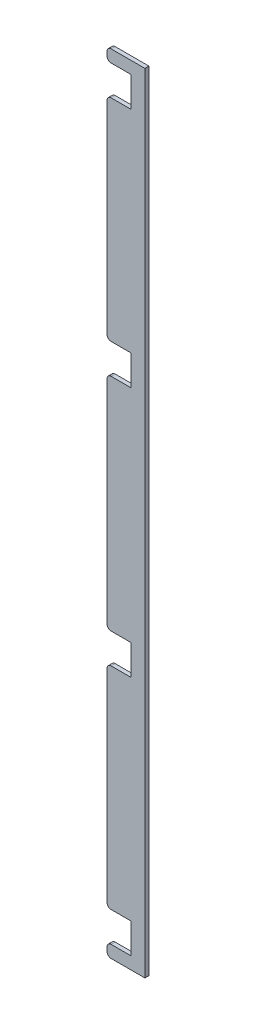
SolidWorks part; units mm, degrees
ref_plane "Front Plane" through (0, 0, 0) normal (0, 0, 1) x (1, 0, 0)
ref_plane "Top Plane" through (0, 0, 0) normal (0, 1, 0) x (1, 0, 0)
ref_plane "Right Plane" through (0, 0, 0) normal (1, 0, 0) x (0, 0, -1)
sketch "Sketch1" plane through (0, 0, 0) normal (0, 0, 1) x (1, 0, 0)
  line L0 (0, -182.5952) -> (-4.5, -182.5952)
  line L2 (0, 13.4048) -> (0, -182.5952)
  line L6 (-4.5, 10.3548) -> (-3.5, 10.3548)
  line L7 (-3.5, 10.3548) -> (-3.5, 2.8548)
  line L8 (0, 2.4048) -> (0, -5.5952) construction
  line L9 (-3.5, 2.8548) -> (-4.5, 2.8548)
  line L10 (-4.5, -49.6452) -> (-3.5, -49.6452)
  line L11 (-3.5, -49.6452) -> (-3.5, -57.1452)
  line L12 (-3.5, -57.1452) -> (-4.5, -57.1452)
  line L13 (-4.5, -112.0452) -> (-3.5, -112.0452)
  line L14 (-3.5, -112.0452) -> (-3.5, -119.5452)
  line L15 (-3.5, -119.5452) -> (-4.5, -119.5452)
  line L16 (-4.5, -172.0452) -> (-3.5, -172.0452)
  line L17 (-3.5, -172.0452) -> (-3.5, -179.5452)
  line L18 (-3.5, -179.5452) -> (-4.5, -179.5452)
  line L100 (-8.4, 10.3548) -> (-4.5, 10.3548)
  line L101 (-4.5, 10.3548) -> (-4.5, 2.8548)
  line L102 (-4.5, 2.8548) -> (-8.4, 2.8548)
  line L103 (-9.4, 1.8548) -> (-9.4, -48.6452)
  line L104 (-8.4, -49.6452) -> (-4.5, -49.6452)
  line L105 (-4.5, -49.6452) -> (-4.5, -57.1452)
  line L106 (-4.5, -57.1452) -> (-8.4, -57.1452)
  line L107 (-9.4, -58.1452) -> (-9.4, -111.0452)
  line L108 (-8.4, -112.0452) -> (-4.5, -112.0452)
  line L109 (-4.5, -112.0452) -> (-4.5, -119.5452)
  line L110 (-4.5, -119.5452) -> (-8.4, -119.5452)
  line L111 (-9.4, -120.5452) -> (-9.4, -171.0452)
  line L112 (-8.4, -172.0452) -> (-4.5, -172.0452)
  line L113 (-4.5, -172.0452) -> (-4.5, -179.5452)
  line L114 (-4.5, -179.5452) -> (-8.4, -179.5452)
  line L115 (-9.4, -180.5452) -> (-9.4, -181.5952)
  line L116 (-8.4, -182.5952) -> (-4.5, -182.5952)
  line L117 (-4.5, -182.5952) -> (-4.5, -191.5952)
  line L118 (-4.5, -191.5952) -> (78.5, -191.5952)
  line L119 (78.5, -191.5952) -> (78.5, -182.5952)
  line L120 (78.5, -182.5952) -> (82.4, -182.5952)
  line L121 (83.4, -181.5952) -> (83.4, -180.5452)
  line L122 (82.4, -179.5452) -> (78.5, -179.5452)
  line L123 (78.5, -179.5452) -> (78.5, -172.0452)
  line L124 (78.5, -172.0452) -> (82.4, -172.0452)
  line L125 (83.4, -171.0452) -> (83.4, -120.5452)
  line L126 (82.4, -119.5452) -> (78.5, -119.5452)
  line L127 (78.5, -119.5452) -> (78.5, -112.0452)
  line L128 (78.5, -112.0452) -> (82.4, -112.0452)
  line L129 (83.4, -111.0452) -> (83.4, -58.1452)
  line L130 (82.4, -57.1452) -> (78.5, -57.1452)
  line L131 (78.5, -57.1452) -> (78.5, -49.6452)
  line L132 (78.5, -49.6452) -> (82.4, -49.6452)
  line L133 (83.4, -48.6452) -> (83.4, 1.8548)
  line L134 (82.4, 2.8548) -> (78.5, 2.8548)
  line L135 (78.5, 2.8548) -> (78.5, 10.3548)
  line L136 (78.5, 10.3548) -> (82.4, 10.3548)
  line L137 (83.4, 11.3548) -> (83.4, 12.4048)
  line L138 (82.4, 13.4048) -> (78.5, 13.4048)
  line L139 (78.5, 13.4048) -> (78.5, 22.4048)
  line L140 (78.5, 22.4048) -> (-4.5, 22.4048)
  line L141 (-4.5, 22.4048) -> (-4.5, 13.4048)
  line L142 (-4.5, 13.4048) -> (-8.4, 13.4048)
  line L143 (-9.4, 12.4048) -> (-9.4, 11.3548)
  line L144 (-8.4, 10.3548) -> (-4.5, 10.3548)
  line L145 (-4.5, 10.3548) -> (-4.5, 2.8548)
  line L146 (-4.5, 2.8548) -> (-8.4, 2.8548)
  line L147 (-9.4, 1.8548) -> (-9.4, -48.6452)
  line L148 (-8.4, -49.6452) -> (-4.5, -49.6452)
  line L149 (-4.5, -49.6452) -> (-4.5, -57.1452)
  line L150 (-4.5, -57.1452) -> (-8.4, -57.1452)
  line L151 (-9.4, -58.1452) -> (-9.4, -111.0452)
  line L152 (-8.4, -112.0452) -> (-4.5, -112.0452)
  line L153 (-4.5, -112.0452) -> (-4.5, -119.5452)
  line L154 (-4.5, -119.5452) -> (-8.4, -119.5452)
  line L155 (-9.4, -120.5452) -> (-9.4, -171.0452)
  line L156 (-8.4, -172.0452) -> (-4.5, -172.0452)
  line L157 (-4.5, -172.0452) -> (-4.5, -179.5452)
  line L158 (-4.5, -179.5452) -> (-8.4, -179.5452)
  line L159 (-9.4, -180.5452) -> (-9.4, -181.5952)
  line L160 (-8.4, -182.5952) -> (-4.5, -182.5952)
  line L186 (0, 13.4048) -> (-8.4, 13.4048)
  line L187 (-9.4, 12.4048) -> (-9.4, 11.3548)
  arc A40 (-8.4, 2.8548) -> (-9.4, 1.8548) centre (-8.4, 1.8548) ccw
  arc A41 (-9.4, -48.6452) -> (-8.4, -49.6452) centre (-8.4, -48.6452) ccw
  arc A42 (-8.4, -57.1452) -> (-9.4, -58.1452) centre (-8.4, -58.1452) ccw
  arc A43 (-9.4, -111.0452) -> (-8.4, -112.0452) centre (-8.4, -111.0452) ccw
  arc A44 (-8.4, -119.5452) -> (-9.4, -120.5452) centre (-8.4, -120.5452) ccw
  arc A45 (-9.4, -171.0452) -> (-8.4, -172.0452) centre (-8.4, -171.0452) ccw
  arc A46 (-8.4, -179.5452) -> (-9.4, -180.5452) centre (-8.4, -180.5452) ccw
  arc A47 (-9.4, -181.5952) -> (-8.4, -182.5952) centre (-8.4, -181.5952) ccw
  arc A48 (82.4, -182.5952) -> (83.4, -181.5952) centre (82.4, -181.5952) ccw
  arc A49 (83.4, -180.5452) -> (82.4, -179.5452) centre (82.4, -180.5452) ccw
  arc A50 (82.4, -172.0452) -> (83.4, -171.0452) centre (82.4, -171.0452) ccw
  arc A51 (83.4, -120.5452) -> (82.4, -119.5452) centre (82.4, -120.5452) ccw
  arc A52 (82.4, -112.0452) -> (83.4, -111.0452) centre (82.4, -111.0452) ccw
  arc A53 (83.4, -58.1452) -> (82.4, -57.1452) centre (82.4, -58.1452) ccw
  arc A54 (82.4, -49.6452) -> (83.4, -48.6452) centre (82.4, -48.6452) ccw
  arc A55 (83.4, 1.8548) -> (82.4, 2.8548) centre (82.4, 1.8548) ccw
  arc A56 (82.4, 10.3548) -> (83.4, 11.3548) centre (82.4, 11.3548) ccw
  arc A57 (83.4, 12.4048) -> (82.4, 13.4048) centre (82.4, 12.4048) ccw
  arc A58 (-8.4, 13.4048) -> (-9.4, 12.4048) centre (-8.4, 12.4048) ccw
  arc A59 (-9.4, 11.3548) -> (-8.4, 10.3548) centre (-8.4, 11.3548) ccw
  arc A60 (-8.4, 2.8548) -> (-9.4, 1.8548) centre (-8.4, 1.8548) ccw
  arc A61 (-9.4, -48.6452) -> (-8.4, -49.6452) centre (-8.4, -48.6452) ccw
  arc A62 (-8.4, -57.1452) -> (-9.4, -58.1452) centre (-8.4, -58.1452) ccw
  arc A63 (-9.4, -111.0452) -> (-8.4, -112.0452) centre (-8.4, -111.0452) ccw
  arc A64 (-8.4, -119.5452) -> (-9.4, -120.5452) centre (-8.4, -120.5452) ccw
  arc A65 (-9.4, -171.0452) -> (-8.4, -172.0452) centre (-8.4, -171.0452) ccw
  arc A66 (-8.4, -179.5452) -> (-9.4, -180.5452) centre (-8.4, -180.5452) ccw
  arc A67 (-9.4, -181.5952) -> (-8.4, -182.5952) centre (-8.4, -181.5952) ccw
  arc A78 (-8.4, 13.4048) -> (-9.4, 12.4048) centre (-8.4, 12.4048) ccw
  arc A79 (-9.4, 11.3548) -> (-8.4, 10.3548) centre (-8.4, 11.3548) ccw
  dimension "D1" = 1
  dimension "D2" = 0
extrude "Boss-Extrude1" add sketch "Sketch1" along normal blind 1 contours L2 region at (-4.508, -84.5952, 0)
